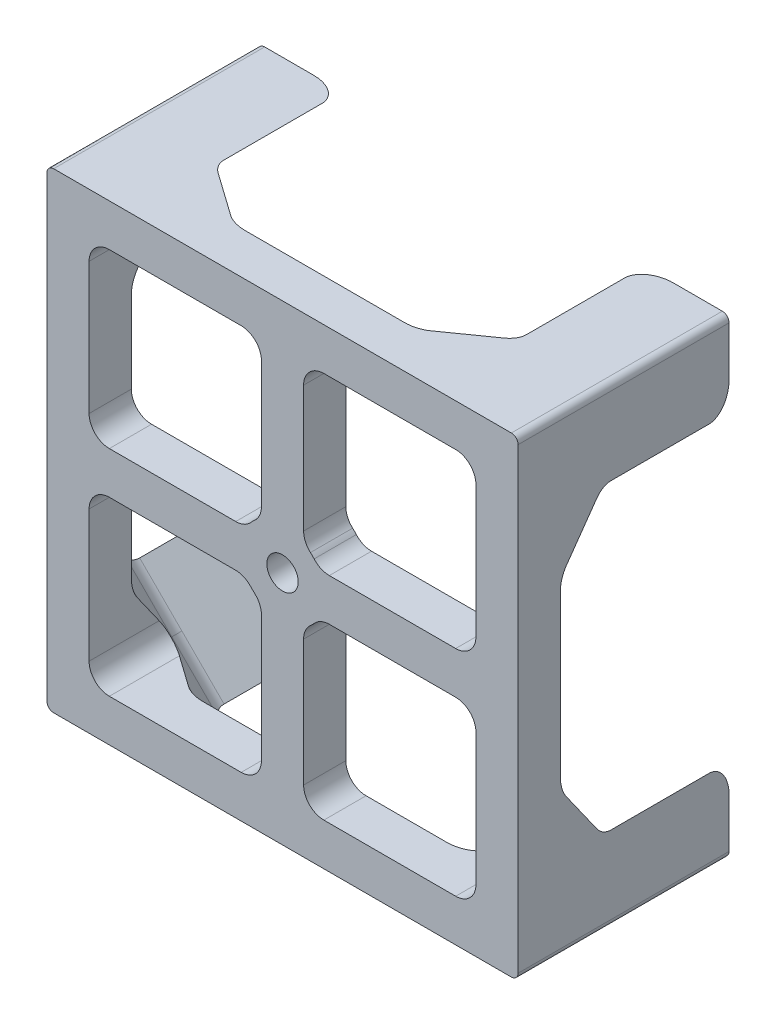
SolidWorks part; units mm, degrees
ref_plane "Front Plane" through (0, 0, 0) normal (0, 0, 1) x (1, 0, 0)
ref_plane "Top Plane" through (0, 0, 0) normal (0, 1, 0) x (1, 0, 0)
ref_plane "Right Plane" through (0, 0, 0) normal (1, 0, 0) x (0, 0, -1)
sketch "Sketch1" plane through (0, 0, 0) normal (0, 0, 1) x (1, 0, 0)
  line L0 (-97.6376, 73.8886) -> (-94.4626, 73.8886)
  line L2 (-94.4626, 73.8886) -> (-97.6376, 70.7136)
  line L4 (-97.6376, 70.7136) -> (-97.6376, 73.8886)
  line L5 (-88.773, 73.8886) -> (-88.773, 56.1594) construction
  line L7 (-88.773, 65.024) -> (-79.9084, 65.024) construction
  line L9 (-79.9084, 70.7136) -> (-79.9084, 73.8886)
  line L10 (-83.0834, 73.8886) -> (-79.9084, 70.7136)
  line L11 (-79.9084, 73.8886) -> (-83.0834, 73.8886)
  line L12 (-79.9084, 56.1594) -> (-83.0834, 56.1594)
  line L13 (-83.0834, 56.1594) -> (-79.9084, 59.3344)
  line L14 (-79.9084, 59.3344) -> (-79.9084, 56.1594)
  line L15 (-97.6376, 59.3344) -> (-97.6376, 56.1594)
  line L16 (-94.4626, 56.1594) -> (-97.6376, 59.3344)
  line L17 (-97.6376, 56.1594) -> (-94.4626, 56.1594)
extrude "Boss-Extrude1" add sketch "Sketch1" along normal blind 6.35
sketch "Sketch2" plane through (0, 0, 6.35) normal (0, 0, 1) x (1, 0, 0)
  line L0 (-88.773, 73.8886) -> (-88.773, 56.1594)
  line L1 (-97.6376, 73.8886) -> (-79.9084, 73.8886)
  line L2 (-97.6376, 73.8886) -> (-97.6376, 56.1594)
  line L3 (-97.6376, 56.1594) -> (-79.9084, 56.1594)
  line L4 (-79.9084, 73.8886) -> (-79.9084, 56.1594)
  line L5 (-97.6376, 73.8886) -> (-79.9084, 56.1594) construction
  line L6 (-97.6376, 56.1594) -> (-79.9084, 73.8886) construction
  line L7 (-97.6376, 65.024) -> (-79.9084, 65.024)
  point P4 (-88.773, 65.024)
extrude "Extrude-Thin1" add sketch "Sketch2" along normal blind 1.5875 separate body thin contours L0 | L7 thin type mid plane wall 1.5875
extrude "Extrude-Thin2" add sketch "Sketch2<3>" along normal blind 1.5875 thin contours L2 L3 L4 L1 thin type one direction reverse wall 1.5875
sketch "Sketch2<3>" plane through (0, 0, 6.35) normal (0, 0, 1) x (1, 0, 0) same geometry as "Sketch2"
sketch "Sketch6" plane through (0, 0, 7.9375) normal (0, 0, 1) x (1, 0, 0)
  line L0 (-89.5668, 65.8177) -> (-87.9793, 64.2302) construction
  circle A0 centre (-88.773, 65.024) radius 1.5875
  dimension "D1" = 3.175
extrude "Boss-Extrude3" add sketch "Sketch6" against normal up to surface (1.5875 mm away) up to face at (-89.0329, 65.1705, 6.35)
hole_wizard "#56 (0.0465) Diameter Hole1" positions "Sketch5" profile "Sketch4" hole size "#56" standard "ANSI Inch" end condition through all
sketch "Sketch5" plane through (0, 0, 7.9375) normal (0, 0, 1) x (1, 0, 0)
  point P6 (-88.773, 65.024)
sketch "Sketch4" plane through (-88.773, 65.024, 7.9375) normal (1, 0, 0) x (0, -1, 0)
  line L0 (0, 0) -> (0, 7.9375)
  line L1 (0, 7.9375) -> (0.5905, 7.9375)
  line L2 (0.5905, 7.9375) -> (0.5905, 0)
  line L5 (0.5905, 0) -> (0, 0)
  line L11 (0, -6.35) -> (0, 107.95) construction
  dimension "Thru Hole Dia." = 1.1811
  dimension "Thru Hole Depth" = 7.9375
chamfer "Chamfer1" distance 1.5875 angle 45 8 edges at (-82.2897, 56.9531, 6.35) (-80.7022, 58.5406, 6.35) (-80.7022, 71.5073, 6.35) (-82.2897, 73.0948, 6.35) (-95.2564, 56.9531, 6.35) (-96.8439, 58.5406, 6.35)
fillet "Fillet2" radius 0.762 20 edges at (-89.5668, 72.3011, 7.1437) (-96.0501, 72.3011, 6.35) (-96.0501, 65.8177, 7.1437) (-90.1478, 65.8177, 7.1437) (-89.5668, 66.3988, 7.1437) (-96.0501, 64.2302, 7.1437) (-96.0501, 57.7469, 6.35) (-89.5668, 57.7469, 7.1437) (-89.5668, 63.6492, 7.1437) (-87.9793, 63.6492, 7.1437) (-87.9793, 57.7469, 7.1437) (-81.4959, 57.7469, 6.35) (-81.4959, 64.2302, 7.1437) (-87.3982, 64.2302, 7.1437) (-87.3982, 65.8177, 7.1437) (-81.4959, 65.8177, 7.1437) (-81.4959, 72.3011, 6.35) (-87.9793, 72.3011, 7.1437) (-87.9793, 66.3988, 7.1437) (-90.1478, 64.2302, 7.1437)
fillet "Fillet3" radius 0.762 20 edges at (-96.8439, 58.5406, 4.7625) (-82.2897, 56.9531, 4.7625) (-80.7022, 71.5073, 4.7625) (-96.8439, 71.5073, 4.7625) (-96.0501, 72.3011, 0) (-81.4959, 72.3011, 0) (-81.4959, 57.7469, 0) (-96.0501, 57.7469, 0) (-95.2564, 56.9531, 4.7625) (-80.7022, 58.5406, 4.7625) (-82.2897, 73.0948, 4.7625) (-96.8439, 60.7857, 6.35) (-93.0113, 56.9531, 6.35) (-84.5347, 73.0948, 6.35) (-80.7022, 69.2623, 6.35) (-80.7022, 60.7857, 6.35) (-84.5347, 56.9531, 6.35) (-93.0113, 73.0948, 6.35) (-96.8439, 69.2623, 6.35) (-95.2564, 73.0948, 4.7625)
fillet "Fillet4" radius 0.254 4 edges at (-79.9084, 56.1594, 3.9688) (-79.9084, 73.8886, 3.9688) (-97.6376, 73.8886, 3.9688) (-97.6376, 56.1594, 3.9688)
